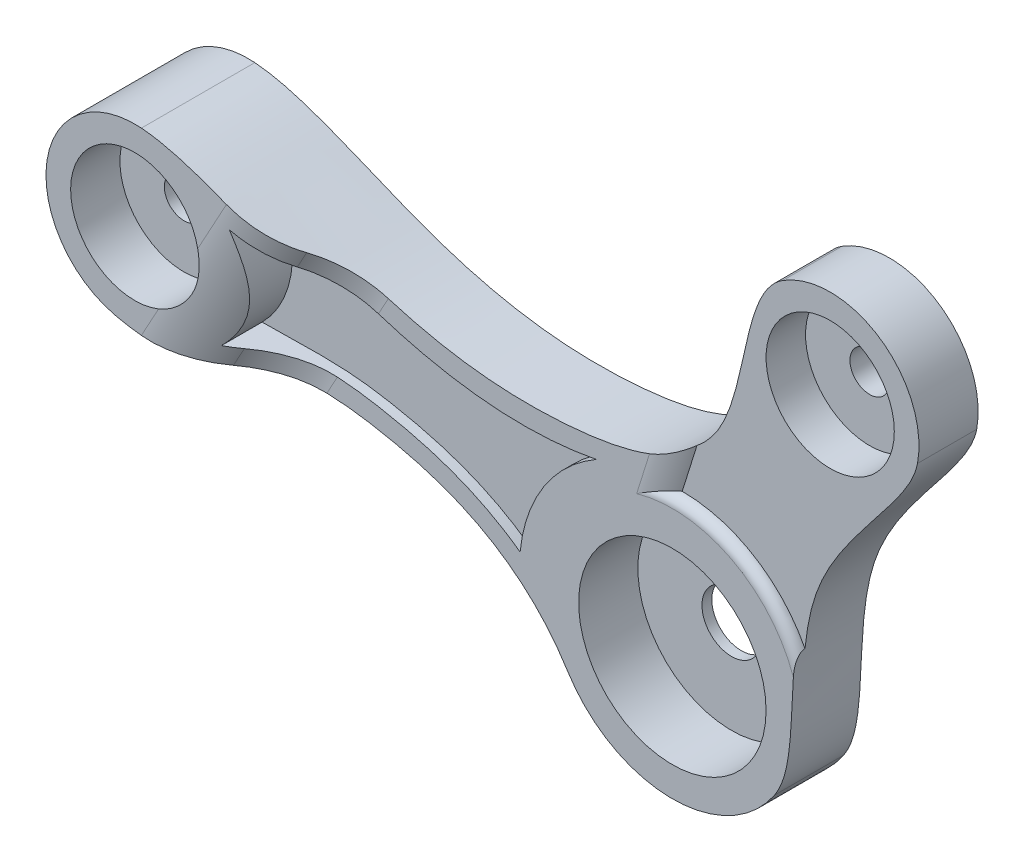
SolidWorks part; units mm, degrees
ref_plane "Front" through (0, 0, 0) normal (0, 0, 1) x (1, 0, 0)
ref_plane "Top" through (0, 0, 0) normal (0, 1, 0) x (1, 0, 0)
ref_plane "Right" through (0, 0, 0) normal (1, 0, 0) x (0, 0, -1)
sketch "Sketch1" plane through (0, 0, 0) normal (0, 0, 1) x (1, 0, 0)
  line L0 (-81.9645, 0) -> (90.5611, 0) construction
  line L1 (0, 55.6757) -> (0, -74.6047) construction
  line L2 (0, 0) -> (-50, 15) construction
  line L3 (0, 0) -> (15, 30) construction
  line L4 (11.9069, 38.694) -> (8.4634, 36.5135) construction
  line L5 (-45.2477, 23.6683) -> (-53.4037, 24.2811) construction
  line L6 (24.3941, 31.3205) -> (23.3081, 25.419) construction
  line L7 (12.6688, -3.569) -> (8.0615, -10.4043) construction
  line L8 (-6.1443, -13.7523) -> (-15.0542, 0.4999) construction
  line L9 (-52.1586, 6.2084) -> (-56.4589, 7.7719) construction
  circle A0 centre (0, 0) radius 9.5
  circle A1 centre (-50, 15) radius 2
  circle A2 centre (-50, 15) radius 6.5
  arc A3 (-49.3257, 23.9747) -> (-53.0752, 6.5417) centre (-50, 15) ccw
  circle A4 centre (15, 30) radius 2
  circle A5 centre (15, 30) radius 6.5
  arc A6 (23.8514, 28.3711) -> (10.1852, 37.6038) centre (15, 30) ccw
  arc A7 (-10.5992, -6.6262) -> (10.3651, -6.9867) centre (0, 0) ccw
  circle A8 centre (0, 0) radius 3
  spline S0 degree 3 poles (-49.3257, 23.9747) (-44.5138, 23.6132) (-30.8882, 16.6055) (-13.9437, 13.5653) (7.4976, 18.1263) (5.9065, 34.8944) (10.1852, 37.6038) knots 0 0 0 0 0.236865 0.54418 0.752586 1 1 1 1
  spline S1 degree 3 poles (-53.0752, 6.5417) (-49.739, 5.3287) (-36.3078, 5.7968) (-29.961, 5.4296) (-15.8017, 1.6956) (-10.5992, -6.6262) knots 0 0 0 0 0.240822 0.551531 1 1 1 1
  spline S2 degree 3 poles (10.3651, -6.9867) (13.1452, -2.8623) (9.1976, 13.4223) (23.0805, 24.1826) (23.8514, 28.3711) knots 0 0 0 0 0.50285 1 1 1 1
  point P5 (-50, 15)
  point P6 (15, 30)
  point P16 (0, 0)
  point P29 (0, 0)
  point P33 (13.6837, 12.1182)
  dimension "D5" = 19
  dimension "D6" = 4
  dimension "D7" = 13
  dimension "D8" = 18
  dimension "D9" = 4
  dimension "D10" = 13
  dimension "D11" = 18
  dimension "D12" = 25
  dimension "D13" = 6
  dimension "D1" = 50
  dimension "D2" = 15
  dimension "D3" = 15
  dimension "D4" = 30
extrude "Boss-Extrude1" add sketch "Sketch1" along normal blind 7 contours A7 S2 A6 S0 A3 S1 A0 A2 A5 | A2 A1 | A0 A8 | A5 A4
sketch "Sketch2" plane through (0, 0, 7) normal (0, 0, 1) x (1, 0, 0)
  circle A0 centre (0, 0) radius 9.5
  dimension "D1" = 19
extrude "Cut-Extrude1" cut sketch "Sketch2" against normal blind 6
sketch "Sketch3" plane through (0, 0, 7) normal (0, 0, 1) x (1, 0, 0)
  circle A0 centre (15, 30) radius 6.5 construction
  circle A1 centre (15, 30) radius 6.5
extrude "Cut-Extrude2" cut sketch "Sketch3" against normal blind 5
sketch "Sketch4" plane through (0, 0, 7) normal (0, 0, 1) x (1, 0, 0)
  line L0 (-32.9124, 18.4239) -> (-39.9031, 5.6096)
  arc A0 (-49.3257, 23.9747) -> (-53.0752, 6.5417) centre (-50, 15) ccw construction
  arc A1 (-49.3257, 23.9747) -> (-53.0752, 6.5417) centre (-50, 15) ccw
  spline S0 degree 3 poles (860.3294, 413.592) (-171.7518, -0.7995) (-44.725, 6.2837) (-17.9131, 4.7327) (113.406, -38.5802) (-601.4504, -813.3846) knots -1.326203 -1.326203 -1.326203 -1.326203 0.240822 0.551531 2.898251 2.898251 2.898251 2.898251 only from (-53.0752, 6.5417) to (-10.5992, -6.6262) construction
  spline S1 degree 3 poles (244.7404, -931.7996) (-121.6821, 89.2202) (-61.6828, 22.1308) (-13.9437, 13.5653) (32.6533, 23.4774) (-55.8951, 154.9527) (703.3947, -683.1314) knots -1.367736 -1.367736 -1.367736 -1.367736 0.236865 0.54418 0.752586 1.895342 1.895342 1.895342 1.895342 only from (-49.3257, 23.9747) to (10.1852, 37.6038) construction
  spline S2 degree 3 poles (-53.0752, 6.5417) (-49.739, 5.3287) (-43.8744, 5.5331) (-39.9031, 5.6096) knots 0 0 0 0 0.240822 0.240822 0.240822 0.240822
  spline S3 degree 3 poles (-49.3257, 23.9747) (-44.5138, 23.6132) (-38.583, 20.563) (-32.9124, 18.4239) knots 0 0 0 0 0.236865 0.236865 0.236865 0.236865
extrude "Boss-Extrude2" add sketch "Sketch4" along normal blind 4.5
sketch "Sketch5" plane through (0, 0, 11.5) normal (0, 0, 1) x (1, 0, 0)
  circle A0 centre (-50, 15) radius 6.5
  dimension "D1" = 13
extrude "Cut-Extrude3" cut sketch "Sketch5" against normal blind 5
sketch "Sketch6" plane through (0, 0, 0) normal (0, 0, -1) x (-1, 0, 0)
  circle A5 centre (0, 0) radius 15.5
  arc A6 (52.3918, 8.4213) -> (49.4756, 21.9803) centre (50, 15) ccw
  arc A7 (-8.7067, -5.8688) -> (8.9033, -5.566) centre (0, 0) ccw
  arc A8 (-11.2551, 35.9141) -> (-21.8844, 28.733) centre (-15, 30) ccw
  arc A12 (15.4321, 1.4495) -> (7.7191, 13.4412) centre (0, 0) ccw
  circle A14 centre (50, 15) radius 10.5
  arc A15 (40.4816, 19.4327) -> (42.5912, 7.5596) centre (50, 15) ccw
  spline S6 degree 3 poles (-395.4845, -456.63) (1614.452, -1976.1397) (-133.3121, -143.9924) (12.9812, -0.5736) (13.3469, -0.236) (14.101, 0.419) (14.4906, 0.7374) (15.684, 1.6545) (16.509, 2.2133) (18.2126, 3.2352) (19.0912, 3.6982) (20.4459, 4.327) (20.9036, 4.5256) (21.8307, 4.902) (22.3009, 5.0799) (23.7146, 5.5795) (24.6653, 5.8686) (26.5795, 6.3763) (27.5433, 6.5945) (29.4792, 6.9848) (30.4504, 7.1626) (32.408, 7.4362) (33.395, 7.5281) (35.3844, 7.6294) (36.3868, 7.6424) (38.3924, 7.638) (39.396, 7.6206) (42.4072, 7.5591) (44.4147, 7.5149) (47.4179, 7.6159) (48.4177, 7.6759) (49.9131, 7.852) (50.4108, 7.9252) (69.4153, 11.6887) (86.4157, 46.02) (8.6878, 2007.2162) knots -12.738112 -12.738112 -12.738112 -12.738112 0.125 0.125 0.15625 0.15625 0.1875 0.1875 0.25 0.25 0.3125 0.3125 0.34375 0.34375 0.375 0.375 0.4375 0.4375 0.5 0.5 0.5625 0.5625 0.625 0.625 0.6875 0.6875 0.75 0.75 0.875 0.875 0.9375 0.9375 0.96875 0.96875 2.133607 2.133607 2.133607 2.133607 only from (8.9033, -5.566) to (52.3918, 8.4213)
  spline S7 degree 3 poles (870.1826, 480.6207) (-8.8858, 53.0789) (-24.6302, 36.182) (-21.6558, 27.9711) (-21.5779, 27.7905) (-21.3244, 27.2581) (-21.1291, 26.9157) (-20.7124, 26.2433) (-20.4902, 25.9136) (-20.0337, 25.2657) (-19.7987, 24.9468) (-19.0827, 23.9981) (-18.5912, 23.3762) (-17.6081, 22.1324) (-17.1161, 21.5108) (-16.1496, 20.2548) (-15.6748, 19.6204) (-14.7578, 18.3276) (-14.3142, 17.6674) (-13.0646, 15.6476) (-12.3408, 14.2542) (-11.5256, 12.048) (-11.2991, 11.2932) (-11.0163, 10.1366) (-10.9314, 9.7463) (-10.7798, 8.9652) (-10.7128, 8.5738) (-10.4154, 6.6127) (-10.2976, 5.0312) (-10.169, 2.6538) (-10.1342, 1.8606) (-10.0521, 0.2752) (-10.0054, -0.517) (-9.8928, -1.7015) (-9.848, -2.0957) (-9.7342, -2.8821) (-9.6651, -3.2752) (-9.4888, -4.0483) (-9.3819, -4.4292) (-4.9042, -16.3827) (32.3963, -21.7681) (641.6892, 753.721) knots -0.659736 -0.659736 -0.659736 -0.659736 0.015625 0.015625 0.03125 0.03125 0.0625 0.0625 0.09375 0.09375 0.125 0.125 0.1875 0.1875 0.25 0.25 0.3125 0.3125 0.375 0.375 0.5 0.5 0.5625 0.5625 0.59375 0.59375 0.625 0.625 0.75 0.75 0.8125 0.8125 0.875 0.875 0.90625 0.90625 0.9375 0.9375 0.96875 0.96875 1.944234 1.944234 1.944234 1.944234 only from (-21.8844, 28.733) to (-8.7067, -5.8688)
  spline S8 degree 3 poles (384.6517, -920.1595) (98.4739, 1.1272) (68.4796, 26.5315) (46.3993, 21.4342) (45.6527, 21.2191) (43.4324, 20.5057) (41.9778, 19.9405) (39.0808, 18.7676) (37.6394, 18.1573) (34.7444, 16.9777) (33.2901, 16.4111) (28.8775, 14.8815) (25.8744, 14.0712) (22.0155, 13.4172) (21.2385, 13.3042) (19.6736, 13.1151) (18.884, 13.039) (16.5126, 12.8687) (14.9319, 12.8325) (12.561, 12.8862) (11.7707, 12.922) (10.1903, 13.0276) (9.3994, 13.0967) (7.0428, 13.3655) (5.4888, 13.6257) (3.2008, 14.2209) (2.4455, 14.4538) (1.3269, 14.8722) (0.9567, 15.0233) (0.2317, 15.3477) (-0.1243, 15.5215) (-1.1705, 16.0811) (-1.8391, 16.5051) (-2.7877, 17.2371) (-3.093, 17.4959) (-3.6707, 18.0366) (-3.9447, 18.3194) (-4.7206, 19.2066) (-5.1747, 19.8512) (-5.7653, 20.8944) (-5.9459, 21.2513) (-6.2772, 21.9714) (-6.4285, 22.3361) (-7.1292, 24.1777) (-7.515, 25.7075) (-8.0446, 28.0181) (-8.212, 28.7911) (-8.5642, 30.3325) (-8.7483, 31.1012) (-9.0781, 32.2413) (-9.197, 32.6181) (-9.4639, 33.3599) (-9.6117, 33.725) (-9.9576, 34.4353) (-10.1568, 34.7827) (-16.8489, 43.6289) (-56.9553, 32.2108) (-296.521, -922.4166) knots -0.847726 -0.847726 -0.847726 -0.847726 0.03125 0.03125 0.0625 0.0625 0.125 0.125 0.1875 0.1875 0.25 0.25 0.375 0.375 0.40625 0.40625 0.4375 0.4375 0.5 0.5 0.53125 0.53125 0.5625 0.5625 0.625 0.625 0.65625 0.65625 0.671875 0.671875 0.6875 0.6875 0.71875 0.71875 0.734375 0.734375 0.75 0.75 0.78125 0.78125 0.796875 0.796875 0.8125 0.8125 0.875 0.875 0.90625 0.90625 0.9375 0.9375 0.953125 0.953125 0.96875 0.96875 0.984375 0.984375 1.407838 1.407838 1.407838 1.407838 only from (49.4756, 21.9803) to (-11.2551, 35.9141)
  spline S9 degree 3 poles (15.4321, 1.4495) (16.0581, 1.9045) (16.7014, 2.3288) (18.2126, 3.2352) (19.0912, 3.6982) (20.4459, 4.327) (20.9036, 4.5256) (21.8307, 4.902) (22.3009, 5.0799) (23.7146, 5.5795) (24.6653, 5.8686) (26.5795, 6.3763) (27.5433, 6.5945) (29.4792, 6.9848) (30.4504, 7.1626) (32.408, 7.4362) (33.395, 7.5281) (35.3844, 7.6294) (36.3868, 7.6424) (38.3924, 7.638) (39.396, 7.6206) (41.1303, 7.5852) (41.8609, 7.5698) (42.5912, 7.5596) knots 0.201619 0.201619 0.201619 0.201619 0.25 0.25 0.3125 0.3125 0.34375 0.34375 0.375 0.375 0.4375 0.4375 0.5 0.5 0.5625 0.5625 0.625 0.625 0.6875 0.6875 0.75 0.75 0.795491 0.795491 0.795491 0.795491
  spline S11 degree 3 poles (40.4816, 19.4327) (39.5372, 19.0427) (38.5976, 18.6375) (36.3851, 17.6868) (35.1121, 17.1419) (31.2602, 15.621) (28.647, 14.7626) (24.6382, 13.782) (23.2871, 13.5064) (21.2346, 13.1816) (20.5462, 13.0882) (19.1601, 12.9329) (18.4624, 12.8713) (14.9867, 12.6499) (12.2176, 12.7452) (8.88, 13.2295) (8.298, 13.328) (7.7191, 13.4412) knots 0.141327 0.141327 0.141327 0.141327 0.1875 0.1875 0.25 0.25 0.375 0.375 0.4375 0.4375 0.46875 0.46875 0.5 0.5 0.625 0.625 0.651363 0.651363 0.651363 0.651363
  dimension "D1" = 2
  dimension "D2" = 6
  dimension "D3" = 4
extrude "Cut-Extrude4" cut sketch "Sketch6" against normal blind 1
sketch "Sketch7" plane through (0, 0, 7) normal (0, 0, 1) x (1, 0, 0)
  arc A0 (-42.5912, 7.5596) -> (-40.4816, 19.4327) centre (-50, 15) ccw construction
  arc A1 (-7.7191, 13.4412) -> (-15.4321, 1.4495) centre (0, 0) ccw construction
  arc A2 (-42.5912, 7.5596) -> (-40.4816, 19.4327) centre (-50, 15) ccw
  arc A3 (-7.7191, 13.4412) -> (-15.4321, 1.4495) centre (0, 0) ccw
  spline S0 degree 3 poles (-773.9963, -1839.1947) (-128.7559, 60.7922) (-83.681, 38.0099) (-36.3851, 17.6868) (-35.1121, 17.1419) (-31.2602, 15.621) (-28.647, 14.7626) (-24.6382, 13.782) (-23.2871, 13.5064) (-21.2346, 13.1816) (-20.5462, 13.0882) (-19.1601, 12.9329) (-18.4624, 12.8713) (-14.9867, 12.6499) (-12.2176, 12.7452) (37.7588, 19.997) (89.6418, 120.1174) (-1917.6691, 597.4402) knots -2.0731 -2.0731 -2.0731 -2.0731 0.1875 0.1875 0.25 0.25 0.375 0.375 0.4375 0.4375 0.46875 0.46875 0.5 0.5 0.625 0.625 2.766484 2.766484 2.766484 2.766484 only from (-40.4816, 19.4327) to (-7.7191, 13.4412) construction
  spline S1 degree 3 poles (-824.7782, -1824.8021) (-16.3718, -251.6696) (36.2885, -29.4568) (-18.2126, 3.2352) (-19.0912, 3.6982) (-20.4459, 4.327) (-20.9036, 4.5256) (-21.8307, 4.902) (-22.3009, 5.0799) (-23.7146, 5.5795) (-24.6653, 5.8686) (-26.5795, 6.3763) (-27.5433, 6.5945) (-29.4792, 6.9848) (-30.4504, 7.1626) (-32.408, 7.4362) (-33.395, 7.5281) (-35.3844, 7.6294) (-36.3868, 7.6424) (-38.3924, 7.638) (-39.396, 7.6206) (-92.5089, 6.535) (-144.7231, 3.3325) (-98.3866, 2004.7462) knots -3.686516 -3.686516 -3.686516 -3.686516 0.25 0.25 0.3125 0.3125 0.34375 0.34375 0.375 0.375 0.4375 0.4375 0.5 0.5 0.5625 0.5625 0.625 0.625 0.6875 0.6875 0.75 0.75 3.994762 3.994762 3.994762 3.994762 only from (-15.4321, 1.4495) to (-42.5912, 7.5596) construction
  spline S2 degree 3 poles (-40.4816, 19.4327) (-39.5372, 19.0427) (-38.5976, 18.6375) (-36.3851, 17.6868) (-35.1121, 17.1419) (-31.2602, 15.621) (-28.647, 14.7626) (-24.6382, 13.782) (-23.2871, 13.5064) (-21.2346, 13.1816) (-20.5462, 13.0882) (-19.1601, 12.9329) (-18.4624, 12.8713) (-14.9867, 12.6499) (-12.2176, 12.7452) (-8.88, 13.2295) (-8.298, 13.328) (-7.7191, 13.4412) knots 0.141327 0.141327 0.141327 0.141327 0.1875 0.1875 0.25 0.25 0.375 0.375 0.4375 0.4375 0.46875 0.46875 0.5 0.5 0.625 0.625 0.651363 0.651363 0.651363 0.651363
  spline S3 degree 3 poles (-15.4321, 1.4495) (-16.0581, 1.9045) (-16.7014, 2.3288) (-18.2126, 3.2352) (-19.0912, 3.6982) (-20.4459, 4.327) (-20.9036, 4.5256) (-21.8307, 4.902) (-22.3009, 5.0799) (-23.7146, 5.5795) (-24.6653, 5.8686) (-26.5795, 6.3763) (-27.5433, 6.5945) (-29.4792, 6.9848) (-30.4504, 7.1626) (-32.408, 7.4362) (-33.395, 7.5281) (-35.3844, 7.6294) (-36.3868, 7.6424) (-38.3924, 7.638) (-39.396, 7.6206) (-41.1303, 7.5852) (-41.8609, 7.5698) (-42.5912, 7.5596) knots 0.201619 0.201619 0.201619 0.201619 0.25 0.25 0.3125 0.3125 0.34375 0.34375 0.375 0.375 0.4375 0.4375 0.5 0.5 0.5625 0.5625 0.625 0.625 0.6875 0.6875 0.75 0.75 0.795491 0.795491 0.795491 0.795491
extrude "Cut-Extrude5" cut sketch "Sketch7" against normal blind 1
sketch "Sketch8" plane through (0, 0, 11.5) normal (0, 0, 1) x (1, 0, 0)
  line L0 (-38.8018, 7.6283) -> (-33.8776, 16.6545)
  line L1 (-39.9031, 5.6096) -> (-32.9124, 18.4239) construction
  arc A0 (-42.5912, 7.5596) -> (-40.4816, 19.4327) centre (-50, 15) ccw construction
  arc A1 (-42.5912, 7.5596) -> (-40.4816, 19.4327) centre (-50, 15) ccw
  spline S0 degree 3 poles (-824.7782, -1824.8021) (-16.3718, -251.6696) (36.2885, -29.4568) (-18.2126, 3.2352) (-19.0912, 3.6982) (-20.4459, 4.327) (-20.9036, 4.5256) (-21.8307, 4.902) (-22.3009, 5.0799) (-23.7146, 5.5795) (-24.6653, 5.8686) (-26.5795, 6.3763) (-27.5433, 6.5945) (-29.4792, 6.9848) (-30.4504, 7.1626) (-32.408, 7.4362) (-33.395, 7.5281) (-35.3844, 7.6294) (-36.3868, 7.6424) (-38.3924, 7.638) (-39.396, 7.6206) (-92.5089, 6.535) (-144.7231, 3.3325) (-98.3866, 2004.7462) knots -3.686516 -3.686516 -3.686516 -3.686516 0.25 0.25 0.3125 0.3125 0.34375 0.34375 0.375 0.375 0.4375 0.4375 0.5 0.5 0.5625 0.5625 0.625 0.625 0.6875 0.6875 0.75 0.75 3.994762 3.994762 3.994762 3.994762 only from (-15.4321, 1.4495) to (-42.5912, 7.5596) construction
  spline S1 degree 3 poles (-773.9963, -1839.1947) (-128.7559, 60.7922) (-83.681, 38.0099) (-36.3851, 17.6868) (-35.1121, 17.1419) (-31.2602, 15.621) (-28.647, 14.7626) (-24.6382, 13.782) (-23.2871, 13.5064) (-21.2346, 13.1816) (-20.5462, 13.0882) (-19.1601, 12.9329) (-18.4624, 12.8713) (-14.9867, 12.6499) (-12.2176, 12.7452) (37.7588, 19.997) (89.6418, 120.1174) (-1917.6691, 597.4402) knots -2.0731 -2.0731 -2.0731 -2.0731 0.1875 0.1875 0.25 0.25 0.375 0.375 0.4375 0.4375 0.46875 0.46875 0.5 0.5 0.625 0.625 2.766484 2.766484 2.766484 2.766484 only from (-40.4816, 19.4327) to (-7.7191, 13.4412) construction
  spline S2 degree 3 poles (-38.8018, 7.6283) (-39.3343, 7.621) (-39.867, 7.611) (-41.1303, 7.5852) (-41.8609, 7.5698) (-42.5912, 7.5596) knots 0.716829 0.716829 0.716829 0.716829 0.75 0.75 0.795491 0.795491 0.795491 0.795491
  spline S3 degree 3 poles (-40.4816, 19.4327) (-39.5372, 19.0427) (-38.5976, 18.6375) (-36.4014, 17.6938) (-35.1448, 17.1559) (-33.8776, 16.6545) knots 0.141327 0.141327 0.141327 0.141327 0.1875 0.1875 0.249197 0.249197 0.249197 0.249197
extrude "Cut-Extrude6" cut sketch "Sketch8" against normal up to next
fillet "Fillet3" radius 10 1 edges at (-33.395, 17.5392, 11.5)
fillet "Fillet4" radius 10 2 edges at (-33.395, 17.5392, 7) (-39.3525, 6.619, 7)
sketch "Sketch9" plane through (0, 0, 7) normal (0, 0, 1) x (1, 0, 0)
  line L0 (0, 14) -> (1.4953, 18.7716)
  arc A1 (23.8514, 28.3711) -> (10.1852, 37.6038) centre (15, 30) ccw construction
  arc A3 (23.8514, 28.3711) -> (10.1852, 37.6038) centre (15, 30) ccw
  circle A7 centre (0, 0) radius 14
  arc A8 (12.4429, 6.4167) -> (0, 14) centre (0, 0) ccw
  spline S0 degree 3 poles (-855.024, 494.1008) (101.8514, -91.1945) (-99.5415, 47.0978) (151.8343, 45.1139) (-976.1012, 35.6421) knots -2.02003 -2.02003 -2.02003 -2.02003 0.50285 3.019111 3.019111 3.019111 3.019111 only from (10.3651, -6.9867) to (23.8514, 28.3711) construction
  spline S1 degree 3 poles (-1007.331, 223.0824) (-71.1049, 149.5597) (-82.1058, -0.9342) (32.6526, 23.4773) (-55.8918, 154.9477) (703.3435, -683.0749) knots -2.18916 -2.18916 -2.18916 -2.18916 0.54418 0.752586 1.895316 1.895316 1.895316 1.895316 only from (-28.7934, 17.0214) to (10.1852, 37.6038) construction
  spline S2 degree 3 poles (12.4429, 6.4167) (12.6494, 8.3474) (14.2931, 17.3716) (23.0805, 24.1826) (23.8514, 28.3711) knots 0.36703 0.36703 0.36703 0.36703 0.50285 1 1 1 1
  spline S3 degree 3 poles (1.4953, 18.7716) (2.2181, 19.3633) (6.9066, 24.3545) (5.9065, 34.8944) (10.1852, 37.6038) knots 0.713485 0.713485 0.713485 0.713485 0.752586 1 1 1 1
  dimension "D1" = 4.5
extrude "Cut-Extrude7" cut sketch "Sketch9" against normal blind 1
fillet "Fillet6" radius 5 1 edges
fillet "Fillet8" radius 1 1 edges at (5.8318, 12.7275, 7)
